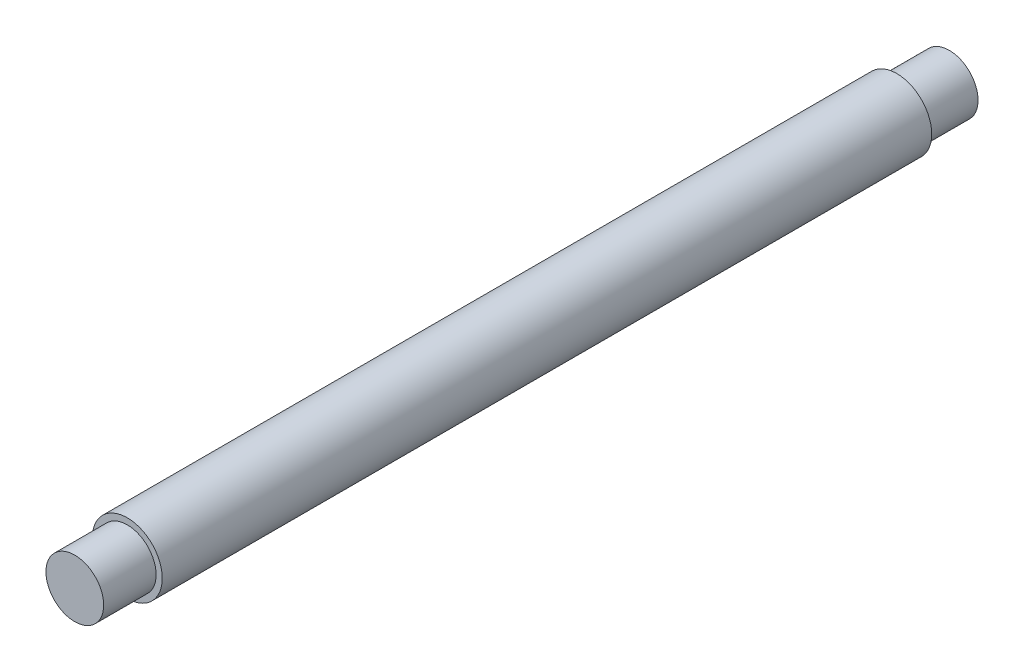
SolidWorks part; units mm, degrees
material "Cast Stainless Steel"
ref_plane "Front Plane" through (0, 0, 0) normal (0, 0, 1) x (1, 0, 0)
ref_plane "Top Plane" through (0, 0, 0) normal (0, 1, 0) x (1, 0, 0)
ref_plane "Right Plane" through (0, 0, 0) normal (1, 0, 0) x (0, 0, -1)
sketch "Sketch2" plane through (0, 0, 0) normal (0, 0, 1) x (1, 0, 0)
  circle A0 centre (0, 0) radius 20
  dimension "D1" = 40
extrude "Boss-Extrude1" add sketch "Sketch2" along normal blind 220 and the other way blind 220
sketch "Sketch3" plane through (0, 0, 220) normal (0, 0, 1) x (1, 0, 0)
  circle A0 centre (0, 0) radius 16.5
  dimension "D1" = 33
extrude "Boss-Extrude2" add sketch "Sketch3" along normal blind 30
sketch "Sketch4" plane through (0, 0, -220) normal (0, 0, -1) x (-1, 0, 0)
  circle A0 centre (0, 0) radius 16.5
  dimension "D1" = 33
extrude "Boss-Extrude3" add sketch "Sketch4" along normal blind 30
sketch "Sketch5" plane through (0, 0, 0) normal (1, 0, 0) x (0, 0, -1)
  line L0 (-215, 0) -> (-215, 15)
  line L1 (-215, 15) -> (215, 15)
  line L2 (215, 15) -> (215, 0)
  line L3 (-220, 16.5) -> (-220, -16.5) construction
  line L4 (220, -20) -> (220, 20) construction
  line L5 (-220, 0) -> (220, 0) construction
  line L6 (-220, 20) -> (-220, -20) construction
  line L7 (-215, 0) -> (215, 0)
  dimension "D1" = 5
  dimension "D2" = 15
  dimension "D3" = 5
revolve "Cut-Revolve1" cut sketch "Sketch5" angle 360 about L7
